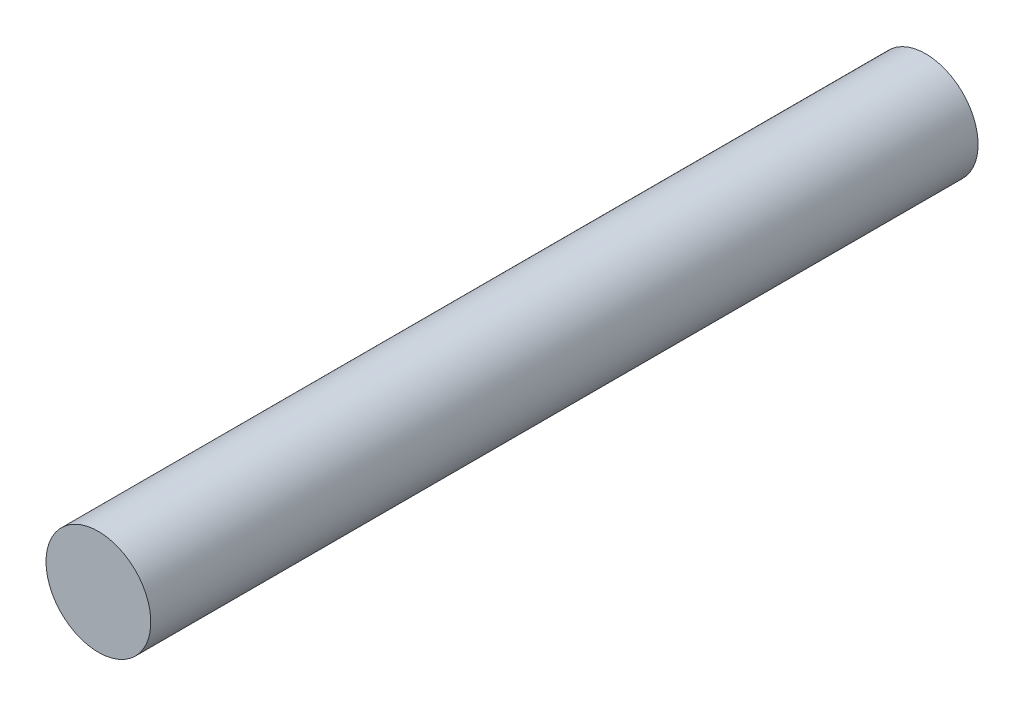
SolidWorks part; units mm, degrees
ref_plane "Front Plane" through (0, 0, 0) normal (0, 0, 1) x (1, 0, 0)
ref_plane "Top Plane" through (0, 0, 0) normal (0, 1, 0) x (1, 0, 0)
ref_plane "Right Plane" through (0, 0, 0) normal (1, 0, 0) x (0, 0, -1)
sketch "Sketch1" plane through (0, 0, 0) normal (0, 0, 1) x (1, 0, 0)
  circle A0 centre (0, 0) radius 4.826
  dimension "D1" = 9.652
extrude "Boss-Extrude2" add sketch "Sketch1" along normal blind 76.2 contours A0
